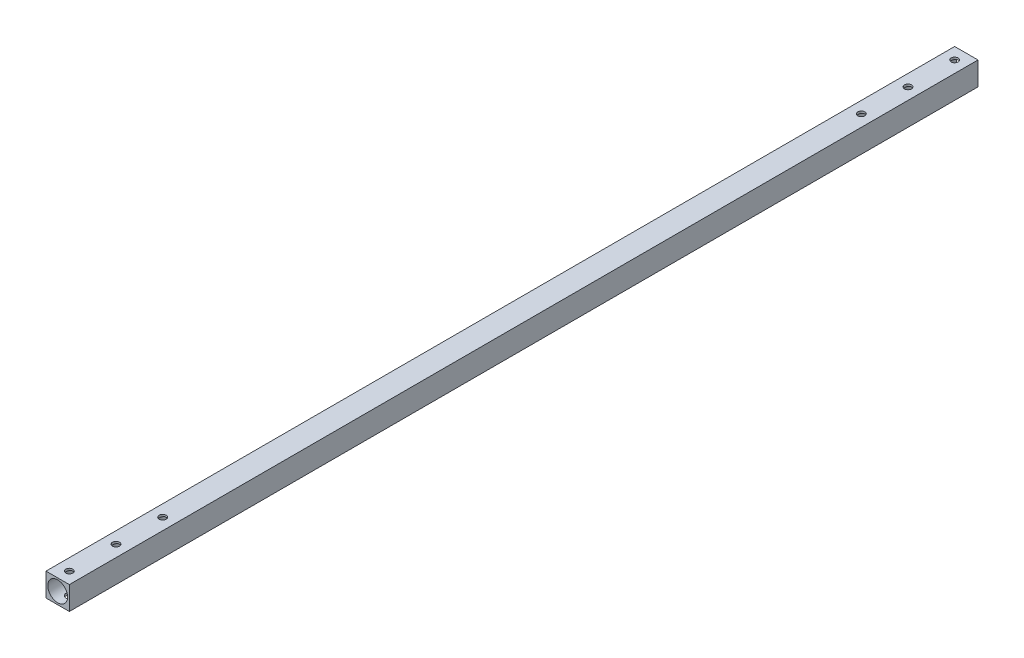
SolidWorks part; units mm, degrees
material "Thornel VCB-20 Carbon Cloth"
ref_plane "Front Plane" through (0, 0, 0) normal (0, 0, 1) x (1, 0, 0)
ref_plane "Top Plane" through (0, 0, 0) normal (0, 1, 0) x (1, 0, 0)
ref_plane "Right Plane" through (0, 0, 0) normal (1, 0, 0) x (0, 0, -1)
sketch "Sketch1" plane through (0, 0, 0) normal (0, 0, 1) x (1, 0, 0)
  line L1 (-5, -5) -> (5, -5)
  line L2 (-5, -5) -> (-5, 5)
  line L3 (-5, 5) -> (5, 5)
  line L4 (5, -5) -> (5, 5)
  line L5 (-5, -5) -> (5, 5) construction
  line L6 (-5, 5) -> (5, -5) construction
  circle A0 centre (0, 0) radius 4.25
  point P0 (0, 0)
  dimension "D3" = 8.5
  dimension "D1" = 10
  dimension "D2" = 10
extrude "Boss-Extrude1" add sketch "Sketch1" along normal blind 389.4
sketch "Sketch2" plane through (0, 5, 0) normal (0, 1, 0) x (1, 0, 0)
  line L0 (0, 0) -> (0, -5) construction
  line L1 (0, -5) -> (0, -25) construction
  line L2 (0, -25) -> (0, -45) construction
  line L3 (0, -389.4) -> (0, -384.4) construction
  line L4 (5, -389.4) -> (-5, -389.4) construction
  line L5 (0, -384.4) -> (0, -364.4) construction
  line L6 (0, -364.4) -> (0, -344.4) construction
  circle A0 centre (0, -5) radius 1.5
  circle A1 centre (0, -25) radius 1.5
  circle A2 centre (0, -45) radius 1.5
  circle A3 centre (0, -384.4) radius 1.5
  circle A4 centre (0, -364.4) radius 1.5
  circle A5 centre (0, -344.4) radius 1.5
  dimension "D3" = 3
  dimension "D4" = 5
  dimension "D6" = 3
  dimension "D1" = 5
  dimension "D2" = 20
  dimension "D5" = 20
extrude "Cut-Extrude1" cut sketch "Sketch2" against normal through all
